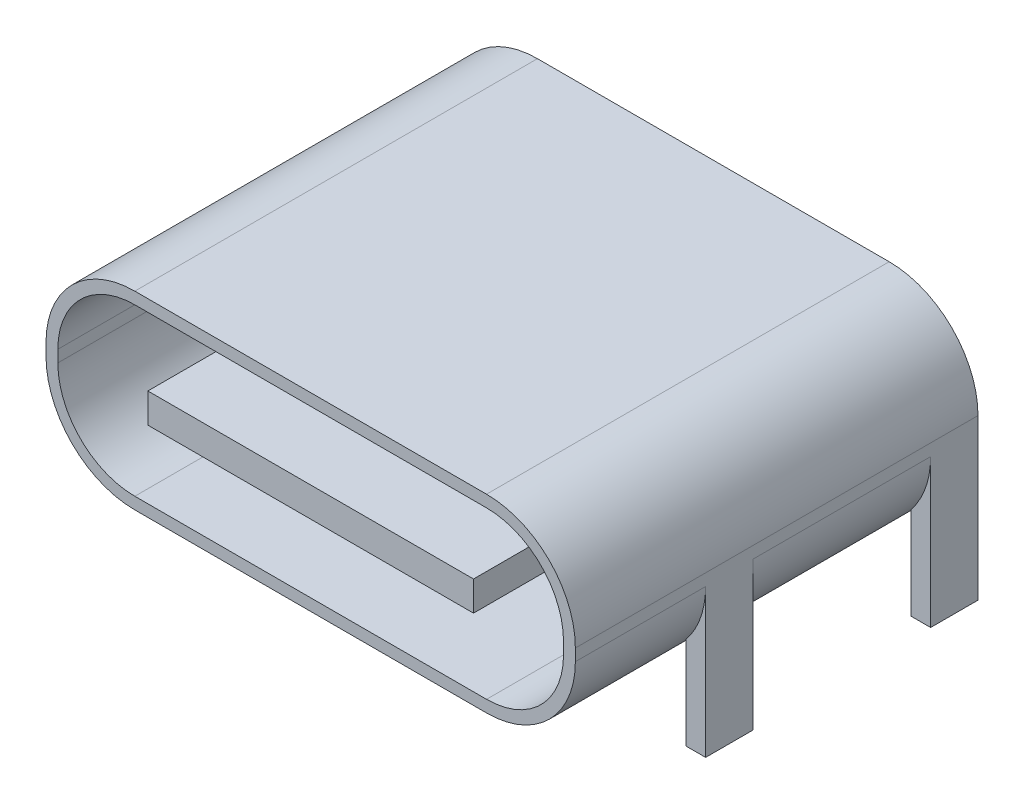
SolidWorks part; units mm, degrees
ref_plane "Front Plane" through (0, 0, 0) normal (0, 0, 1) x (1, 0, 0)
ref_plane "Top Plane" through (0, 0, 0) normal (0, 1, 0) x (1, 0, 0)
ref_plane "Right Plane" through (0, 0, 0) normal (1, 0, 0) x (0, 0, -1)
sketch "Sketch1" plane through (0, 0, 0) normal (0, 0, 1) x (1, 0, 0)
  line L1 (-2.97, 1.6) -> (2.97, 1.6)
  line L2 (-4.47, 0.1) -> (-4.47, -0.1)
  line L3 (-2.97, -1.6) -> (2.97, -1.6)
  line L4 (4.47, 0.1) -> (4.47, -0.1)
  line L5 (-4.47, 1.6) -> (4.47, -1.6) construction
  line L6 (-4.47, -1.6) -> (4.47, 1.6) construction
  arc A0 (-4.47, -0.1) -> (-2.97, -1.6) centre (-2.97, -0.1) ccw
  arc A1 (2.97, -1.6) -> (4.47, -0.1) centre (2.97, -0.1) ccw
  arc A2 (2.97, 1.6) -> (4.47, 0.1) centre (2.97, 0.1) cw
  arc A3 (-2.97, 1.6) -> (-4.47, 0.1) centre (-2.97, 0.1) ccw
  point P0 (0, 0)
  dimension "D3" = 1.5
  dimension "D1" = 3.2
  dimension "D2" = 8.94
extrude "Boss-Extrude1" add sketch "Sketch1" along normal blind 6.8
sketch "Sketch2" plane through (0, -1.6, 0) normal (0, -1, 0) x (1, 0, 0)
  line L1 (-4.47, 4.6) -> (-4.1349, 4.6)
  line L2 (-4.47, 4.6) -> (-4.47, 3.8)
  line L3 (-4.47, 3.8) -> (-4.1349, 3.8)
  line L4 (-4.1349, 4.6) -> (-4.1349, 3.8)
  line L5 (-4.47, 0.8) -> (-4.1349, 0.8)
  line L6 (-4.47, 0.8) -> (-4.47, 0)
  line L7 (-4.47, 0) -> (-4.1349, 0)
  line L8 (-4.1349, 0.8) -> (-4.1349, 0)
  line L9 (4.1349, 0.8) -> (4.47, 0.8)
  line L10 (4.1349, 0.8) -> (4.1349, 0)
  line L11 (4.1349, 0) -> (4.47, 0)
  line L12 (4.47, 0.8) -> (4.47, 0)
  line L13 (4.1349, 4.6) -> (4.47, 4.6)
  line L14 (4.1349, 4.6) -> (4.1349, 3.8)
  line L15 (4.1349, 3.8) -> (4.47, 3.8)
  line L16 (4.47, 4.6) -> (4.47, 3.8)
  line L17 (-4.47, 4.2) -> (-4.1349, 4.2) construction
  line L18 (-2.97, 6.8) -> (-4.47, 6.8) construction
  line L19 (-4.47, 6.8) -> (-4.47, 0) construction
  line L20 (4.47, 6.8) -> (4.47, 0) construction
  line L21 (-4.47, 0) -> (-2.97, 0) construction
  line L22 (-4.47, 0.4) -> (-4.1349, 0.4) construction
  dimension "D1" = 0.8
  dimension "D2" = 2.6
  dimension "D3" = 3.8
extrude "Boss-Extrude2" add sketch "Sketch2" against normal up to next and the other way blind 1
sketch "Sketch3" plane through (0, 0, 6.8) normal (0, 0, 1) x (1, 0, 0)
  line L0 (-2.97, -1.4) -> (2.97, -1.4)
  line L1 (4.27, -0.1) -> (4.27, 0.1)
  line L2 (2.97, 1.4) -> (-2.97, 1.4)
  line L3 (-4.27, 0.1) -> (-4.27, -0.1)
  line L4 (-2.97, -1.6) -> (2.97, -1.6)
  line L5 (4.47, -0.1) -> (4.47, 0.1)
  line L6 (2.97, 1.6) -> (-2.97, 1.6)
  line L7 (-4.47, 0.1) -> (-4.47, -0.1)
  line L8 (-2.97, -1.6) -> (2.97, -1.6) construction
  line L9 (4.47, -0.1) -> (4.47, 0.1) construction
  line L10 (2.97, 1.6) -> (-2.97, 1.6) construction
  line L11 (-4.47, 0.1) -> (-4.47, -0.1) construction
  line L13 (-2.75, 0.25) -> (2.75, 0.25)
  line L14 (-2.75, 0.25) -> (-2.75, -0.25)
  line L15 (-2.75, -0.25) -> (2.75, -0.25)
  line L16 (2.75, 0.25) -> (2.75, -0.25)
  line L17 (-2.75, 0.25) -> (2.75, -0.25) construction
  line L18 (-2.75, -0.25) -> (2.75, 0.25) construction
  arc A0 (2.97, -1.4) -> (4.27, -0.1) centre (2.97, -0.1) ccw
  arc A1 (4.27, 0.1) -> (2.97, 1.4) centre (2.97, 0.1) ccw
  arc A2 (-2.97, 1.4) -> (-4.27, 0.1) centre (-2.97, 0.1) ccw
  arc A3 (-4.27, -0.1) -> (-2.97, -1.4) centre (-2.97, -0.1) ccw
  arc A4 (-4.47, -0.1) -> (-2.97, -1.6) centre (-2.97, -0.1) ccw
  arc A5 (2.97, -1.6) -> (4.47, -0.1) centre (2.97, -0.1) ccw
  arc A6 (4.47, 0.1) -> (2.97, 1.6) centre (2.97, 0.1) ccw
  arc A7 (-2.97, 1.6) -> (-4.47, 0.1) centre (-2.97, 0.1) ccw
  arc A8 (-4.47, -0.1) -> (-2.97, -1.6) centre (-2.97, -0.1) ccw construction
  arc A9 (2.97, -1.6) -> (4.47, -0.1) centre (2.97, -0.1) ccw construction
  arc A10 (4.47, 0.1) -> (2.97, 1.6) centre (2.97, 0.1) ccw construction
  arc A11 (-2.97, 1.6) -> (-4.47, 0.1) centre (-2.97, 0.1) ccw construction
  point P24 (0, 0)
  dimension "D3" = 0.5
  dimension "D4" = 5.5
  dimension "D1" = 0
  dimension "D2" = 0.2
extrude "Cut-Extrude1" cut sketch "Sketch3" against normal blind 5
